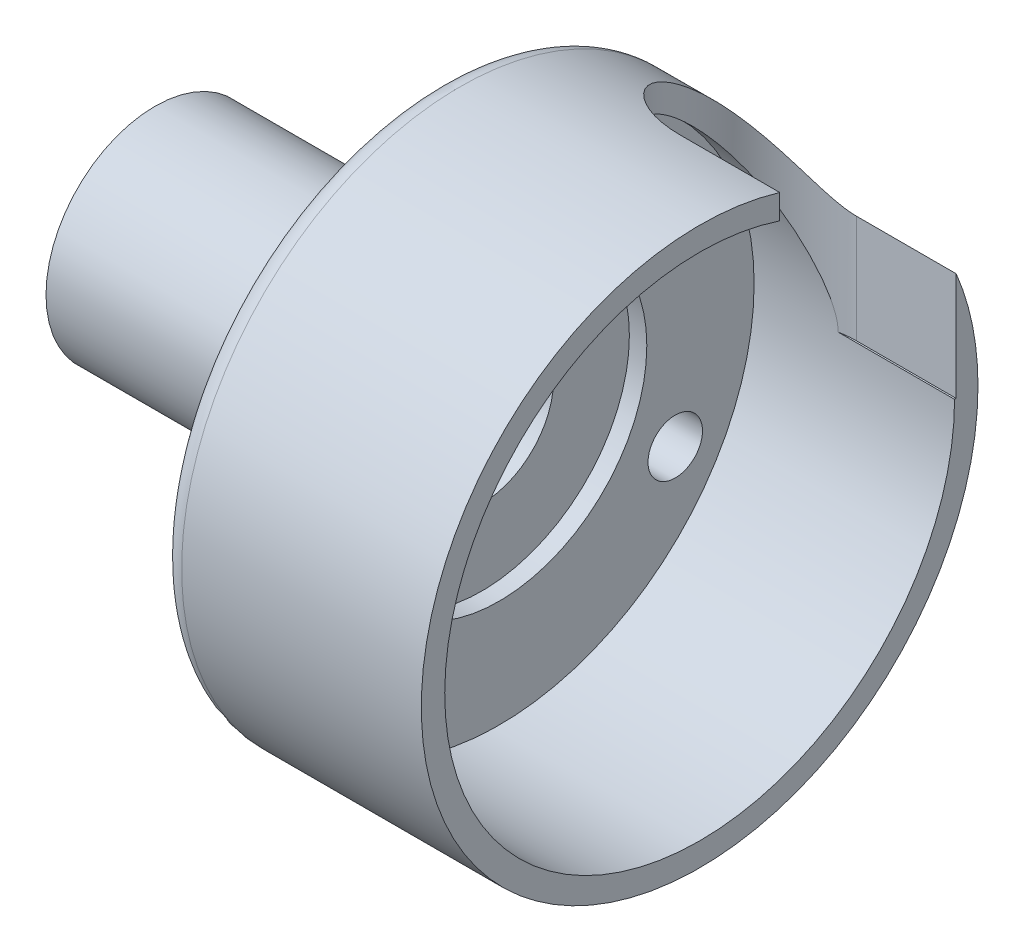
SolidWorks part; units mm, degrees
ref_plane "Front Plane" through (0, 0, 0) normal (0, 0, 1) x (1, 0, 0)
ref_plane "Top Plane" through (0, 0, 0) normal (0, 1, 0) x (1, 0, 0)
ref_plane "Right Plane" through (0, 0, 0) normal (1, 0, 0) x (0, 0, -1)
sketch "Sketch3" plane through (0, 0, 0) normal (1, 0, 0) x (0, 0, -1)
  circle A0 centre (0, 0) radius 5
  circle A1 centre (0, 0) radius 3.3
  dimension "D1" = 10
  dimension "D2" = 6.6
extrude "Boss-Extrude3" add sketch "Sketch3" along normal blind 10 and the other way blind 5 contours A1 | A0 region at (0, 0, 0)
sketch "Sketch10" plane through (10, 0, 0) normal (1, 0, 0) x (0, 0, -1)
  circle A0 centre (0, 0) radius 12.775
  circle A1 centre (0, 0) radius 2.1
  circle A2 centre (0, 0) radius 3.65
  circle M5 centre (0, 0) radius 3.3
  dimension "D1" = 1.55
  dimension "D2" = 4.2
  dimension "D3" = 25.55
extrude "Boss-Extrude5" add sketch "Sketch10" against normal blind 2 contours M5 | A0 region at (10, 0, 3.2067)
sketch "Sketch11" plane through (10, 0, 0) normal (1, 0, 0) x (0, 0, -1)
  circle A0 centre (0, 0) radius 6.775
  circle A1 centre (0, 0) radius 11.275
  circle M2 centre (0, 0) radius 3.3
  dimension "D1" = 13.55
  dimension "D2" = 22.55
extrude "Boss-Extrude6" add sketch "Sketch11" along normal blind 0.8 contours M2 | A0 M2 | A1 region at (10, 0, 6.5834) region at (10, 0, 0)
sketch "Sketch12" plane through (10.8, 0, 0) normal (1, 0, 0) x (0, 0, -1)
  line L1 (0, 9.33) -> (-8.08, -4.665)
  line L2 (-8.08, -4.665) -> (8.08, -4.665)
  line L3 (8.08, -4.665) -> (0, 9.33)
  circle A0 centre (0, 0) radius 4.665 construction
  circle A1 centre (0, 0) radius 11.275 construction
  circle A2 centre (-8.08, -4.665) radius 1.25
  circle A3 centre (8.08, -4.665) radius 1.25
  circle A4 centre (0, 9.33) radius 1.25
  dimension "D2" = 2.5
  dimension "D3" = 2.5
  dimension "D4" = 2.5
  dimension "D1" = 9.33
extrude "Cut-Extrude2" cut sketch "Sketch12" against normal blind 2.75 contours L2 A3 L3 | L3 A4 L1 | L1 A4 L3 | L3 A3 L2 | A2 region at (10.8, 8.5342, 0) region at (10.8, 9.4892, 0) region at (10.8, -4.7446, -8.2178) region at (10.8, -4.2671, -7.3909)
fillet "Fillet3" radius 1 1 edges at (8, 0, -12.775)
sketch "Sketch13" plane through (10, 0, 0) normal (1, 0, 0) x (0, 0, -1)
  circle A0 centre (0, 0) radius 11.275 construction
  circle A1 centre (0, 0) radius 11.275
  circle A2 centre (0, 0) radius 12.775 construction
  circle A3 centre (0, 0) radius 12.775
extrude "Boss-Extrude7" add sketch "Sketch13" along normal blind 10
sketch "Sketch14" plane through (20, 0, 0) normal (1, 0, 0) x (0, 0, -1)
  circle A0 centre (0, 0) radius 11.7
  dimension "D1" = 23.4
extrude "Cut-Extrude3" cut sketch "Sketch14" against normal up to surface (9.2 mm away) up to face at (10.8, 9.33, -1.25)
sketch "Sketch15" plane through (0, 0, 0) normal (0, 1, 0) x (1, 0, 0)
  line L0 (15.4301, 3.675) -> (20, 3.675)
  line L1 (20, -12.775) -> (20, 12.775) construction
  line L2 (15.4301, 11.775) -> (20, 11.775)
  line L3 (20, 11.775) -> (20, 3.675)
  line L4 (20, 12.775) -> (9, 12.775) construction
  line L5 (20, 12.775) -> (9, 12.775)
  arc A0 (15.4301, 11.775) -> (15.4301, 3.675) centre (15.4301, 7.725) ccw
  dimension "D1" = 8.1
  dimension "D2" = 1
extrude "Cut-Extrude5" cut sketch "Sketch15" along normal blind 16 contours L3 L0 A0 L2
sketch "Sketch16" plane through (-5, 0, 0) normal (-1, 0, 0) x (0, 0, 1)
  circle A0 centre (0, 0) radius 4
  dimension "D1" = 8
extrude "Cut-Extrude6" cut sketch "Sketch16" against normal blind 14
